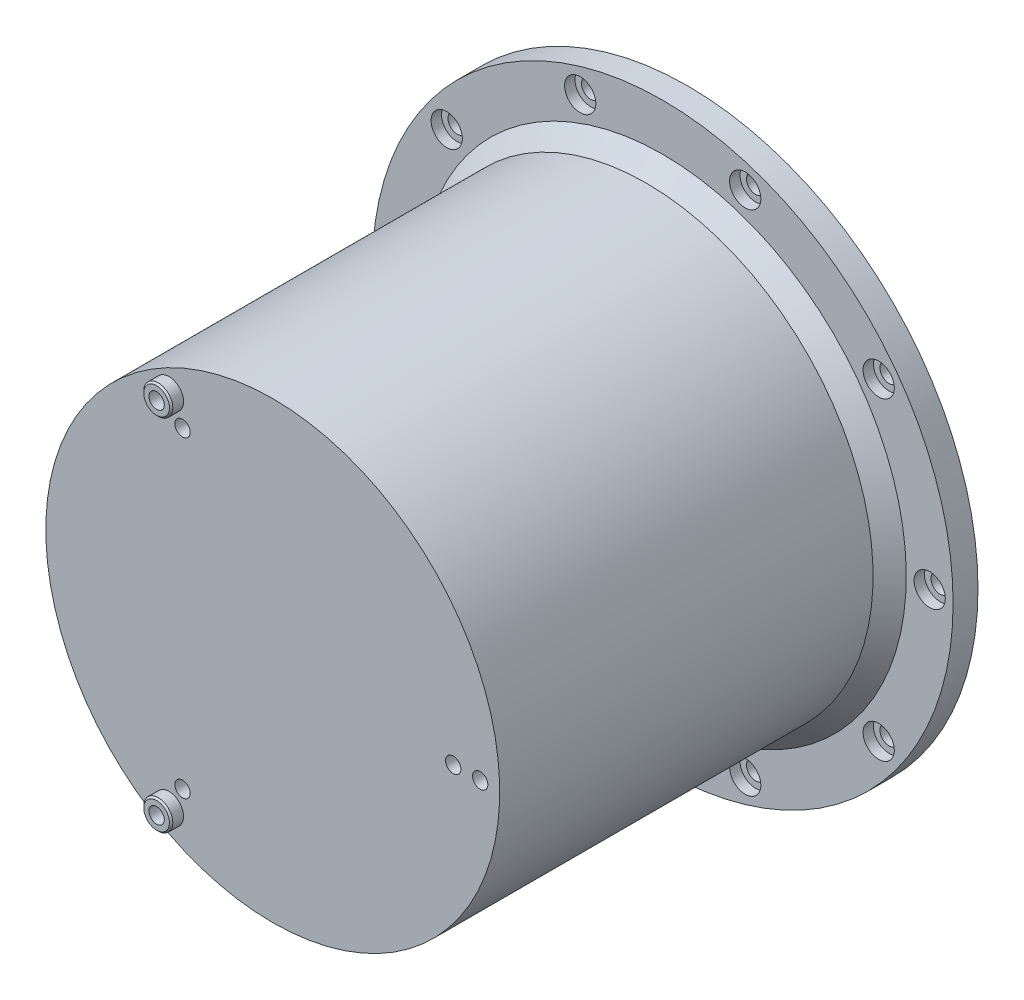
SolidWorks part; units mm, degrees
ref_plane "Piano frontale" through (0, 0, 0) normal (0, 0, 1) x (1, 0, 0)
ref_plane "Piano superiore" through (0, 0, 0) normal (0, 1, 0) x (1, 0, 0)
ref_plane "Piano destro" through (0, 0, 0) normal (1, 0, 0) x (0, 0, -1)
sketch "Schizzo1" plane through (0, 0, -132.2078) normal (0, 0, -1) x (-1, 0, 0)
  circle A14 centre (214.1711, -331.6849) radius 273.5326
  arc A15 (311.7735, -587.2115) -> (380.5507, -548.7976) centre (214.1711, -331.6849) ccw construction
  arc A16 (-35.8289, -322.4349) -> (-35.8289, -340.9349) centre (-35.8289, -331.6849) ccw construction
  arc A17 (-35.8289, -340.9349) -> (-35.8289, -322.4349) centre (-35.8289, -331.6849) ccw construction
  arc A18 (-3.3289, -340.9349) -> (-3.3289, -322.4349) centre (-3.3289, -331.6849) ccw construction
  arc A19 (-3.3289, -322.4349) -> (-3.3289, -340.9349) centre (-3.3289, -331.6849) ccw construction
  arc A20 (322.9211, -134.0744) -> (322.9211, -152.5744) centre (322.9211, -143.3244) ccw construction
  arc A21 (322.9211, -152.5744) -> (322.9211, -134.0744) centre (322.9211, -143.3244) ccw construction
  arc A22 (339.1711, -124.4286) -> (339.1711, -105.9286) centre (339.1711, -115.1786) ccw construction
  arc A23 (339.1711, -105.9286) -> (339.1711, -124.4286) centre (339.1711, -115.1786) ccw construction
  arc A24 (322.9211, -529.2954) -> (322.9211, -510.7954) centre (322.9211, -520.0454) ccw construction
  arc A25 (322.9211, -510.7954) -> (322.9211, -529.2954) centre (322.9211, -520.0454) ccw construction
  arc A26 (339.1711, -557.4413) -> (339.1711, -538.9413) centre (339.1711, -548.1913) ccw construction
  arc A27 (339.1711, -538.9413) -> (339.1711, -557.4413) centre (339.1711, -548.1913) ccw construction
  arc A28 (-35.8289, -322.4349) -> (-35.8289, -340.9349) centre (-35.8289, -331.6849) ccw
  arc A29 (-35.8289, -340.9349) -> (-35.8289, -322.4349) centre (-35.8289, -331.6849) ccw
  arc A30 (-3.3289, -340.9349) -> (-3.3289, -322.4349) centre (-3.3289, -331.6849) ccw
  arc A31 (-3.3289, -322.4349) -> (-3.3289, -340.9349) centre (-3.3289, -331.6849) ccw
  arc A32 (322.9211, -134.0744) -> (322.9211, -152.5744) centre (322.9211, -143.3244) ccw
  arc A33 (322.9211, -152.5744) -> (322.9211, -134.0744) centre (322.9211, -143.3244) ccw
  arc A34 (339.1711, -124.4286) -> (339.1711, -105.9286) centre (339.1711, -115.1786) ccw
  arc A35 (339.1711, -105.9286) -> (339.1711, -124.4286) centre (339.1711, -115.1786) ccw
  arc A36 (322.9211, -529.2954) -> (322.9211, -510.7954) centre (322.9211, -520.0454) ccw
  arc A37 (322.9211, -510.7954) -> (322.9211, -529.2954) centre (322.9211, -520.0454) ccw
  arc A38 (339.1711, -557.4413) -> (339.1711, -538.9413) centre (339.1711, -548.1913) ccw
  arc A39 (339.1711, -538.9413) -> (339.1711, -557.4413) centre (339.1711, -548.1913) ccw
extrude "Estrusione-Estrusione1" add sketch "Schizzo1" along normal blind 15
sketch "Schizzo5" plane through (0, 0, -147.2078) normal (0, 0, -1) x (-1, 0, 0)
  circle A0 centre (214.1711, -331.6849) radius 273.5326 construction
  circle A1 centre (214.1711, -331.6849) radius 273.5326
extrude "Estrusione-Estrusione4" add sketch "Schizzo5" along normal blind 485
sketch "Schizzo6" plane through (0, 0, -632.2078) normal (0, 0, -1) x (-1, 0, 0)
  circle A0 centre (214.1711, -331.6849) radius 350
  dimension "D1" = 700
extrude "Estrusione-Estrusione5" add sketch "Schizzo6" against normal blind 30
chamfer "Smusso2" distance 20 angle 45 1 edges at (-214.1711, -58.1523, -602.2078)
sketch "Schizzo7" plane through (0, 0, -602.2078) normal (0, 0, 1) x (1, 0, 0)
  line L0 (135.8289, -331.6849) -> (107.5952, -331.6849) construction
  line L1 (107.5952, -331.6849) -> (79.3615, -331.6849) construction
  circle A0 centre (-214.1711, -331.6849) radius 321.7663
  circle A1 centre (-214.1711, -331.6849) radius 350 construction
  circle A2 centre (-214.1711, -331.6849) radius 293.5326 construction
  point P11 (107.5952, -331.6849)
hole_wizard "Foro lamato per Bullone M20 a testa esagonale-1" positions "Schizzo3D1" profile "Schizzo9" counterbore size "M20" standard "ISO" end condition through all
sketch3d "Schizzo3D1"
  point P0 (107.5952, -331.6849, -602.2078)
sketch "Schizzo9" plane through (107.5952, -331.6849, -602.2078) normal (1, 0, 0) x (0, -1, 0)
  line L0 (0, 0) -> (0, 30)
  line L1 (0, 30) -> (11, 30)
  line L3 (11, 30) -> (11, 12.5)
  line L4 (11, 12.5) -> (18.8205, 12.5)
  line L5 (18.8205, 12.5) -> (18.8205, 0)
  line L7 (18.8205, 0) -> (0, 0)
  line L11 (0, -6.35) -> (0, 107.95) construction
  dimension "Thru Hole Dia." = 22
  dimension "Thru Hole Depth" = 30
  dimension "C'Bore Dia." = 37.641
  dimension "C'Bore Depth" = 12.5
pattern_circular "RipetizioneCircolare1" count 10 every 36 about axis through (-214.1711, -331.6849, -132.2078) along (0, 0, -1) of "Foro lamato per Bullone M20 a testa esagonale-1"
sketch "Schizzo10" plane through (0, 0, -132.2078) normal (0, 0, 1) x (1, 0, 0)
  arc A0 (-339.1711, -132.6786) -> (-339.1711, -97.6786) centre (-339.1711, -115.1786) ccw construction
  arc A1 (-339.1711, -97.6786) -> (-339.1711, -132.6786) centre (-339.1711, -115.1786) ccw construction
  arc A2 (-339.1711, -565.6913) -> (-339.1711, -530.6913) centre (-339.1711, -548.1913) ccw construction
  arc A3 (-339.1711, -530.6913) -> (-339.1711, -565.6913) centre (-339.1711, -548.1913) ccw construction
  arc A4 (-339.1711, -132.6786) -> (-339.1711, -97.6786) centre (-339.1711, -115.1786) ccw
  arc A5 (-339.1711, -97.6786) -> (-339.1711, -132.6786) centre (-339.1711, -115.1786) ccw
  arc A6 (-339.1711, -565.6913) -> (-339.1711, -530.6913) centre (-339.1711, -548.1913) ccw
  arc A7 (-339.1711, -530.6913) -> (-339.1711, -565.6913) centre (-339.1711, -548.1913) ccw
  circle A8 centre (-339.1711, -548.1913) radius 9.25 construction
  circle A9 centre (-339.1711, -115.1786) radius 9.25 construction
  circle A10 centre (-339.1711, -548.1913) radius 9.25
  circle A11 centre (-339.1711, -115.1786) radius 9.25
extrude "Estrusione-Estrusione6" add sketch "Schizzo10" along normal blind 15
chamfer "Smusso3" distance 2 angle 45 2 edges at (-321.6711, -115.1786, -117.2078) (-321.6711, -548.1913, -117.2078)
